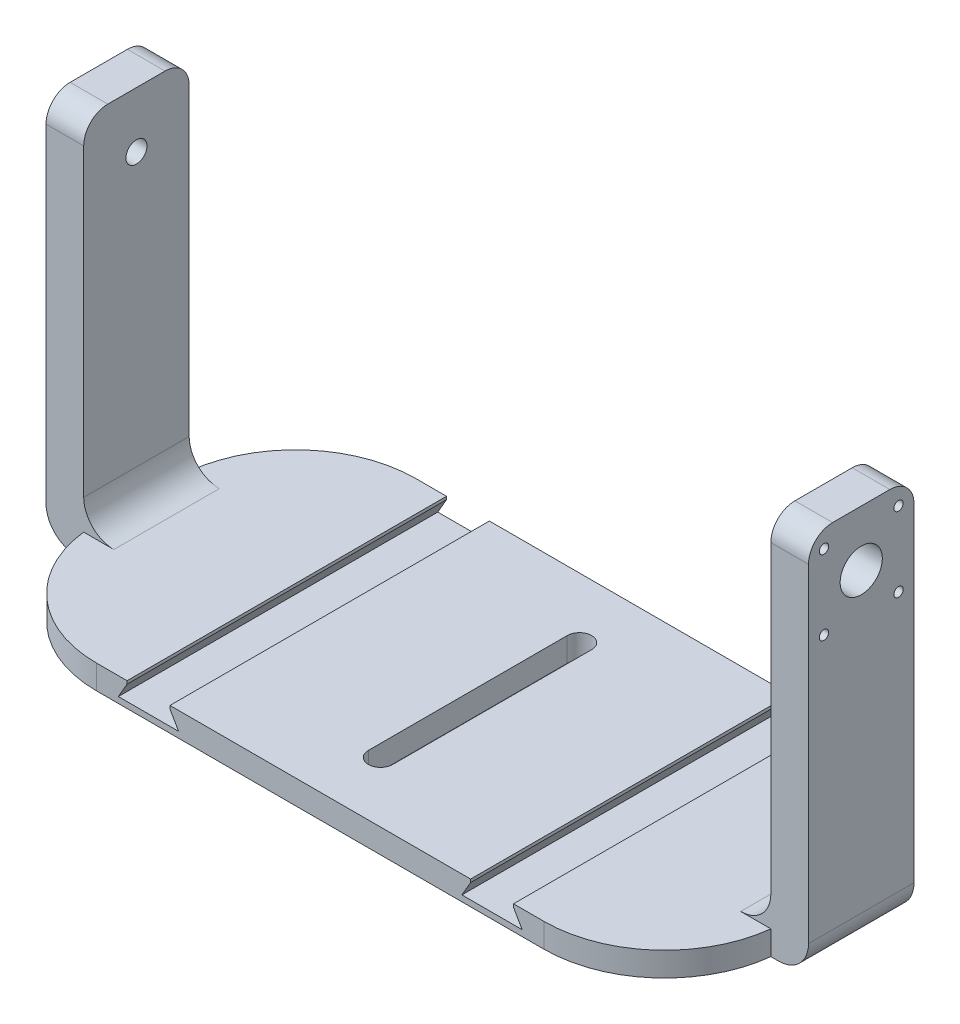
SolidWorks part; units mm, degrees
ref_plane "Front Plane" through (0, 0, 0) normal (0, 0, 1) x (1, 0, 0)
ref_plane "Top Plane" through (0, 0, 0) normal (0, 1, 0) x (1, 0, 0)
ref_plane "Right Plane" through (0, 0, 0) normal (1, 0, 0) x (0, 0, -1)
sketch "Sketch1" plane through (0, 0, 0) normal (0, 0, 1) x (1, 0, 0)
  line L0 (114, 8) -> (114, 0) construction
  line L1 (0, 0) -> (228, 0)
  line L2 (0, 0) -> (0, 8)
  line L3 (0, 8) -> (228, 8)
  line L4 (228, 0) -> (228, 8)
  line L5 (49.8868, 8) -> (49.8868, 7)
  line L7 (178.1132, 8) -> (163.8868, 8)
  line L8 (163.8868, 8) -> (163.8868, 7)
  line L9 (163.8868, 7) -> (161, 2)
  line L10 (161, 2) -> (181, 2)
  line L11 (178.1132, 8) -> (178.1132, 7)
  line L12 (178.1132, 7) -> (181, 2)
  line L13 (114, 4) -> (228, 4) construction
  line L14 (49.8868, 8) -> (64.1132, 8)
  line L15 (171, 2) -> (171, 8) construction
  line L16 (64.1132, 8) -> (64.1132, 7)
  line L17 (64.1132, 7) -> (67, 2)
  line L18 (67, 2) -> (47, 2)
  line L19 (49.8868, 7) -> (47, 2)
  line L25 (228, 0) -> (240.5, 0)
  line L26 (228, 0) -> (228, 127)
  line L27 (228, 127) -> (240.5, 127)
  line L28 (240.5, 0) -> (240.5, 127)
  line L29 (0, 0) -> (-12.5, 0)
  line L30 (0, 0) -> (0, 127)
  line L31 (0, 127) -> (-12.5, 127)
  line L32 (-12.5, 0) -> (-12.5, 127)
  point P7 (171, 4)
  dimension "D1" = 228
  dimension "D2" = 8
  dimension "D3" = 1
  dimension "D4" = 1
  dimension "D5" = 60
  dimension "D6" = 60
  dimension "D7" = 20
  dimension "D8" = 2
  dimension "D9" = 12.5
  dimension "D10" = 127
  dimension "D11" = 12.5
  dimension "D12" = 127
extrude "Boss-Extrude1" add sketch "Sketch1" against normal blind 106 contours L19 L5 L3 L2 L1 L4 L11 L12 L10 L9 L8 L16 L17 L18 | L26 L25 L28 L27 | L30 L29 L32 L31 region at (114, 3.9008, 0)
sketch "Sketch2" plane through (0, 127, 0) normal (0, 1, 0) x (1, 0, 0)
  line L0 (0, 106) -> (0, 0) construction
  line L1 (-12.5, 106) -> (0, 106)
  line L2 (-12.5, 106) -> (-12.5, 70.5)
  line L3 (-12.5, 70.5) -> (0, 70.5)
  line L4 (0, 106) -> (0, 70.5)
  line L5 (228, 106) -> (228, 0) construction
  line L6 (-12.5, 0) -> (0, 0)
  line L7 (-12.5, 0) -> (-12.5, 35.5)
  line L8 (-12.5, 35.5) -> (0, 35.5)
  line L9 (0, 0) -> (0, 35.5)
  line L10 (240.5, 106) -> (228, 106)
  line L11 (240.5, 106) -> (240.5, 70.5)
  line L12 (240.5, 70.5) -> (228, 70.5)
  line L13 (228, 106) -> (228, 70.5)
  line L14 (0, 106) -> (228, 106) construction
  line L15 (240.5, 0) -> (228, 0)
  line L16 (240.5, 0) -> (240.5, 35.5)
  line L17 (240.5, 35.5) -> (228, 35.5)
  line L18 (228, 0) -> (228, 35.5)
  line L19 (114, 106) -> (114, 0) construction
  line L20 (64.1132, 0) -> (163.8868, 0) construction
  line L21 (114, 20) -> (114, 86) construction
  line L22 (109.95, 20) -> (109.95, 86)
  line L23 (118.05, 20) -> (118.05, 86)
  line L24 (0, 53) -> (228, 53) construction
  line L27 (0, 106) -> (0, 0) construction
  line L28 (228, 106) -> (228, 0) construction
  arc A0 (109.95, 20) -> (118.05, 20) centre (114, 20) ccw
  arc A1 (118.05, 86) -> (109.95, 86) centre (114, 86) ccw
  point P30 (114, 53)
  point P35 (114, 90.05)
  point P36 (114, 15.95)
  point P41 (114, 106)
  point P44 (114, 53)
  dimension "D1" = 35
  dimension "D2" = 35.5
  dimension "D3" = 35.5
  dimension "D4" = 35
  dimension "D5" = 74.1
  dimension "D6" = 8.1
extrude "Cut-Extrude1" cut sketch "Sketch2" against normal blind 200
sketch "Sketch4" plane through (240.5, 0, 0) normal (1, 0, 0) x (0, 0, -1)
  line L0 (70.5, 0) -> (35.5, 0) construction
  line L1 (70.5, 127) -> (35.5, 127) construction
  line L2 (53, 127) -> (53, 0) construction
  line L3 (53, 115.5) -> (53, 101.5) construction
  line L4 (53, 108.5) -> (35.5, 108.5) construction
  line L5 (35.5, 0) -> (35.5, 127) construction
  circle A0 centre (53, 108.5) radius 6
  circle A2 centre (53, 108.5) radius 7
  circle A3 centre (40.625, 120.875) radius 1.55
  circle A4 centre (40.625, 96.125) radius 1.55
  circle A5 centre (65.375, 96.125) radius 1.55
  circle A6 centre (65.375, 120.875) radius 1.55
  dimension "D1" = 12
  dimension "D3" = 101.5
  dimension "D4" = 14
  dimension "D7" = 3.1
  dimension "D8" = 3.1
  dimension "D5" = 12.375
  dimension "D10" = 12.375
extrude "Cut-Extrude3" cut sketch "Sketch4<4>" against normal blind 37 from offset 0 contours A0 region at (240.5, 108.5, -53)
sketch "Sketch4<4>" plane through (240.5, 0, 0) normal (1, 0, 0) x (0, 0, -1) same geometry as "Sketch4"
extrude "Cut-Extrude4" cut sketch "Sketch4" against normal blind 18.375 contours A2 A0 | A6 | A5 | A4 | A3 region at (240.5, 108.5, -46.198)
fillet "Fillet3" radius 8 4 edges at (234.25, 127, -70.5) (234.25, 127, -35.5) (-6.25, 127, -70.5) (-6.25, 127, -35.5)
fillet "Fillet4" radius 10 4 edges at (228, 8, -53) (240.5, 0, -53) (-12.5, 0, -53) (0, 8, -53)
fillet "Fillet5" radius 40 4 edges at (228, 4, -106) (0, 4, -106) (0, 4, 0) (228, 4, 0)
sketch "Sketch5" plane through (0, 0, 0) normal (1, 0, 0) x (0, 0, -1)
  line L0 (62.5, 127) -> (43.5, 127) construction
  line L1 (35.5, 18) -> (35.5, 119) construction
  circle A0 centre (53, 108.5) radius 9.5
  circle A1 centre (53, 108.5) radius 3.5
  dimension "D1" = 19
  dimension "D2" = 7
  dimension "D3" = 18.5
  dimension "D4" = 17.5
extrude "Cut-Extrude5" cut sketch "Sketch5" against normal blind 25 contours A1
extrude "Cut-Extrude6" cut sketch "Sketch5<3>" against normal blind 7 from offset 6 offset against normal yes
sketch "Sketch5<3>" plane through (0, 0, 0) normal (1, 0, 0) x (0, 0, -1) same geometry as "Sketch5"
